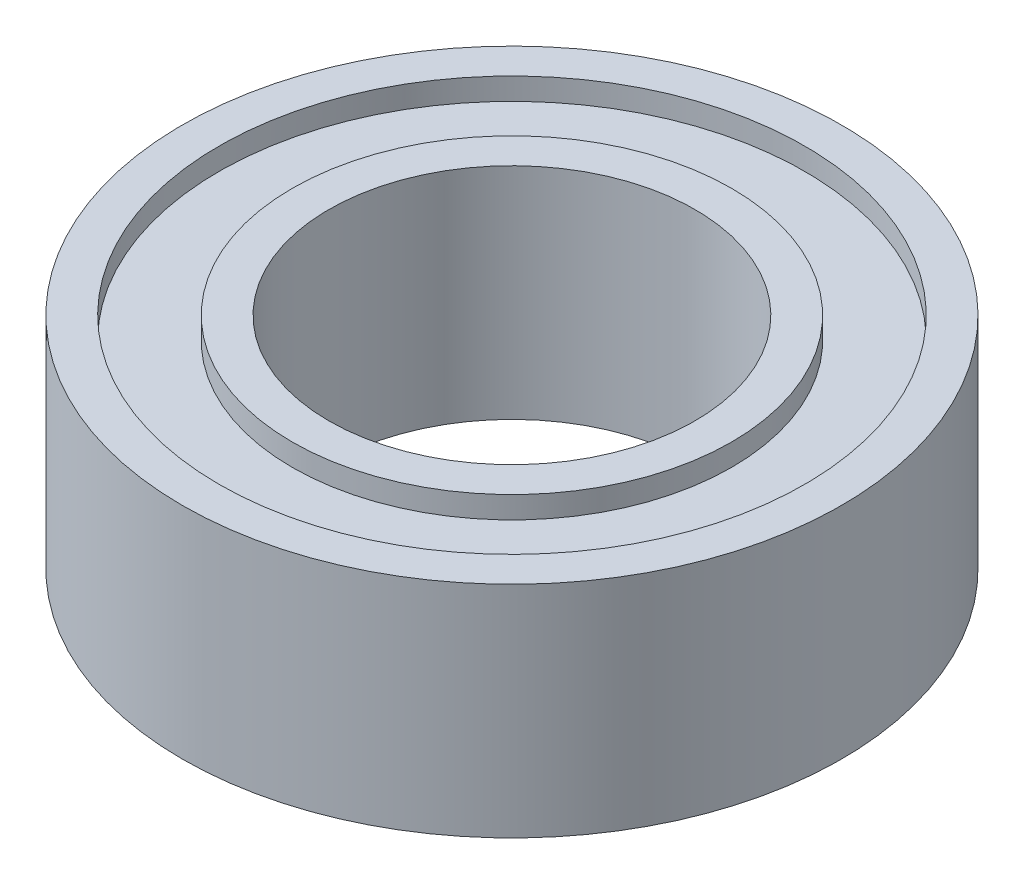
SolidWorks part; units mm, degrees
ref_plane "前视基准面" through (0, 0, 0) normal (0, 0, 1) x (1, 0, 0)
ref_plane "上视基准面" through (0, 0, 0) normal (0, 1, 0) x (1, 0, 0)
ref_plane "右视基准面" through (0, 0, 0) normal (1, 0, 0) x (0, 0, -1)
other "Configuration Table"
sketch "草图1" plane through (0, 0, 0) normal (0, 1, 0) x (1, 0, 0)
  circle A0 centre (0, 0) radius 2.5
  circle A1 centre (0, 0) radius 3
  circle A2 centre (0, 0) radius 4
  circle A3 centre (0, 0) radius 4.5
  dimension "D1" = 5
  dimension "D2" = 0.5
  dimension "D3" = 9
  dimension "D4" = 8
extrude "凸台-拉伸1" add sketch "草图1" along normal blind 1.5 and the other way blind 1.5 contours A3 A2 | A1 A0 region at (-2.9151, 0, 0) region at (-4.3727, 0, 0)
sketch "草图2" plane through (0, 0, 0) normal (0, 1, 0) x (1, 0, 0)
  circle A0 centre (0, 0) radius 3
  circle A1 centre (0, 0) radius 4
  circle A2 centre (0, 0) radius 3 construction
  circle A3 centre (0, 0) radius 4 construction
extrude "凸台-拉伸2" add sketch "草图2" along normal blind 1.2 and the other way blind 1.2
